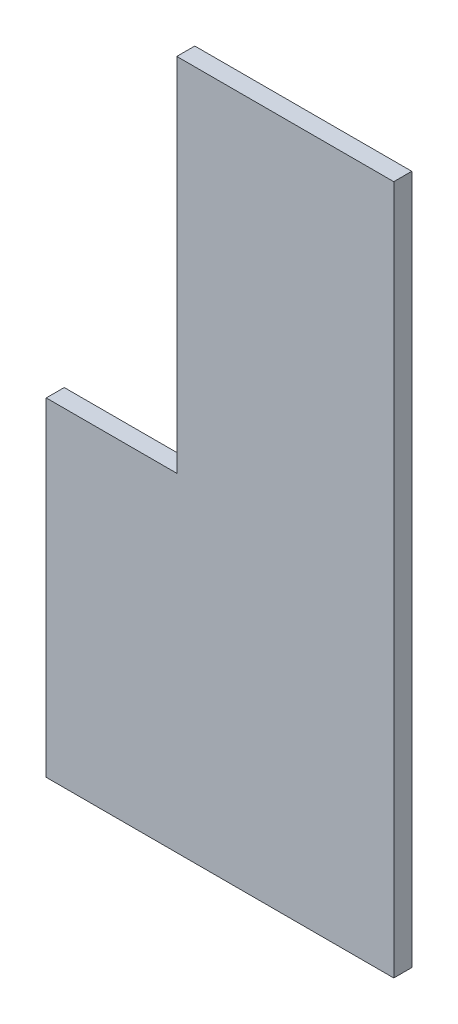
SolidWorks part; units mm, degrees
ref_plane "Ön Düzlem" through (0, 0, 0) normal (0, 0, 1) x (1, 0, 0)
ref_plane "Üst Düzlem" through (0, 0, 0) normal (0, 1, 0) x (1, 0, 0)
ref_plane "Sağ Düzlem" through (0, 0, 0) normal (1, 0, 0) x (0, 0, -1)
sketch "Çizim1" plane through (0, 0, 0) normal (0, 0, 1) x (1, 0, 0)
  line L0 (0, 0) -> (0, 365)
  line L1 (0, 365) -> (145, 365)
  line L2 (145, 365) -> (145, 766)
  line L3 (145, 766) -> (386, 766)
  line L4 (386, 766) -> (386, 0)
  line L5 (386, 0) -> (0, 0)
  dimension "D1" = 386
  dimension "D2" = 766
  dimension "D3" = 365
  dimension "D4" = 145
  dimension "D5" = 401
base flange "Taban-Flanş1" sketch "Çizim1" thickness 20 reverse thickness direction no parameters "D1"=5
sketch "Büküm-Çizgileri1" [suppressed] plane through (0, 0, 0) normal (0, 1, 0) x (1, 0, 0)
sketch "Sınırlandırma-Kutusu1" [suppressed] plane through (0, 0, 0) normal (0, 1, 0) x (1, 0, 0)
sheet metal parameters "Sac-Levha1" thickness 20 parameters "D1"=5
flat pattern "Düz-Çoğaltma1" [suppressed]
sketch "Büküm-Çizgileri2" plane through (0, 0, 0) normal (0, 1, 0) x (1, 0, 0)
sketch3d "Sınırlandırma-Kutusu2" [suppressed]
  line L0 (386, 766, 0) -> (386, 0, 0) construction
  line L1 (0, 766, 0) -> (0, 0, 0) construction
  line L2 (386, 766, 0) -> (0, 766, 0) construction
  line L3 (386, 0, 0) -> (0, 0, 0) construction
